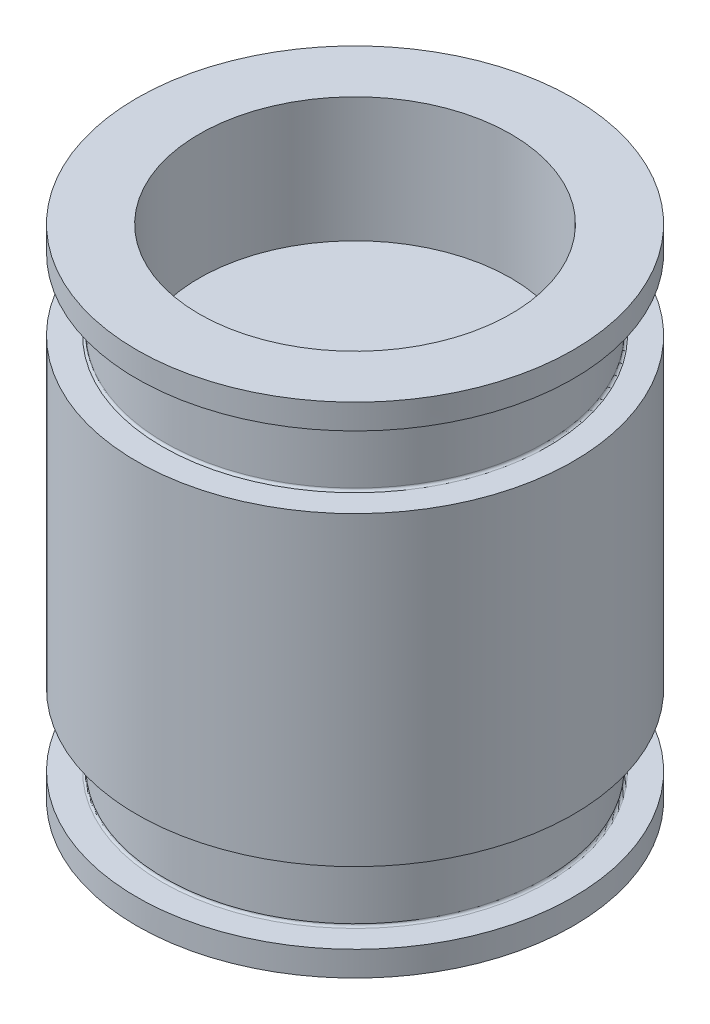
SolidWorks part; units mm, degrees
material "6063-T6"
ref_plane "Front Plane" through (0, 0, 0) normal (0, 0, 1) x (1, 0, 0)
ref_plane "Top Plane" through (0, 0, 0) normal (0, 1, 0) x (1, 0, 0)
ref_plane "Right Plane" through (0, 0, 0) normal (1, 0, 0) x (0, 0, -1)
sketch "Sketch1" plane through (0, 0, 0) normal (0, 1, 0) x (1, 0, 0)
  circle A0 centre (0, 0) radius 22.225
  dimension "D1" = 44.45
extrude "Boss-Extrude1" add sketch "Sketch1" along normal mid plane 50.8
sketch "Sketch2" plane through (0, 25.4, 0) normal (0, 1, 0) x (1, 0, 0)
  circle A0 centre (0, 0) radius 15.875
  dimension "D1" = 31.75
extrude "\"lightening hole\"" cut sketch "Sketch2" against normal blind 12.7
sketch "main-o-ring" plane through (0, 0, 0) normal (0, 0, 1) x (1, 0, 0)
  line L0 (0, 0) -> (0, 33.5592) construction
  line L1 (-22.225, 22.86) -> (-22.225, 15.5702)
  line L2 (-22.225, 22.86) -> (-19.6204, 22.86)
  line L3 (-19.3802, 22.6198) -> (-19.3802, 15.8104)
  line L4 (-19.6204, 15.5702) -> (-22.225, 15.5702)
  line L5 (22.225, 25.4) -> (-22.225, 25.4) construction
  arc A0 (-19.3802, 15.8104) -> (-19.6204, 15.5702) centre (-19.6204, 15.8104) cw
  arc A1 (-19.6204, 22.86) -> (-19.3802, 22.6198) centre (-19.6204, 22.6198) cw
  dimension "D5" = 0.2402
  dimension "D1" = 44.45
  dimension "D2" = 7.2898
  dimension "D3" = 2.54
  dimension "D4" = 2.8448
revolve "o-ring-main (with backup rings)" cut sketch "main-o-ring" angle 360 about L0
mirror "Mirror1" about plane through (0, 0, 0) normal (0, 1, 0) of "o-ring-main (with backup rings)", "\"lightening hole\""
